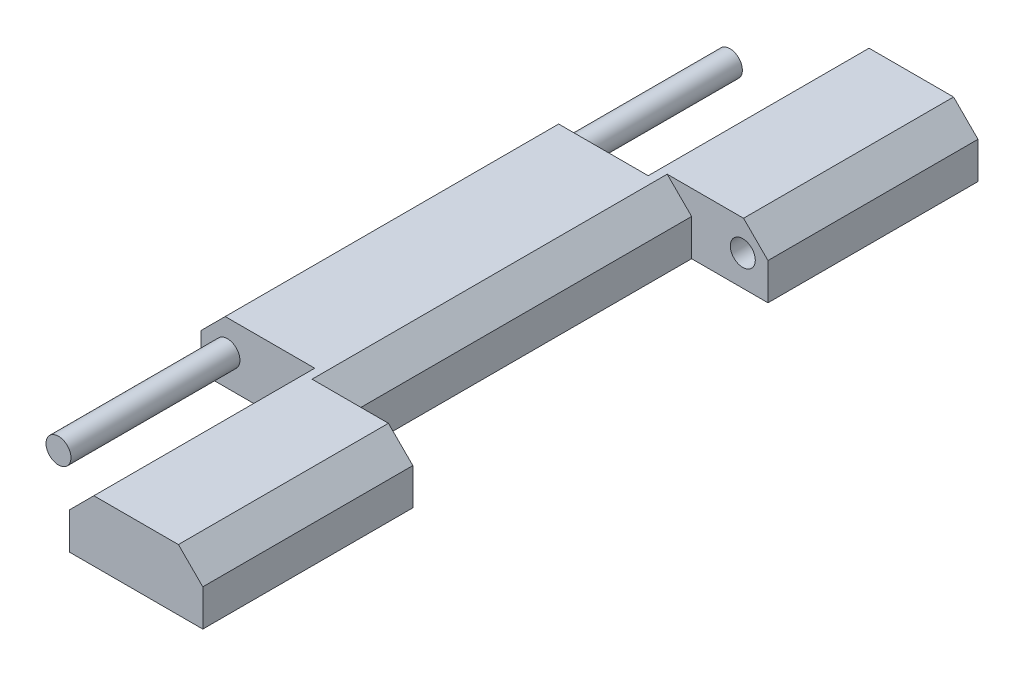
SolidWorks part; units mm, degrees
ref_plane "Front Plane" through (0, 0, 0) normal (0, 0, 1) x (1, 0, 0)
ref_plane "Top Plane" through (0, 0, 0) normal (0, 1, 0) x (1, 0, 0)
ref_plane "Right Plane" through (0, 0, 0) normal (1, 0, 0) x (0, 0, -1)
sketch "Sketch1" plane through (0, 0, 0) normal (0, 1, 0) x (1, 0, 0)
  line L0 (5.4621, -14.5454) -> (5.4621, -31.75)
  line L1 (-5.4621, 31.75) -> (5.4621, 31.75)
  line L2 (-5.4621, 31.75) -> (-5.4621, 13.6578)
  line L3 (-5.4621, -31.75) -> (5.4621, -31.75)
  line L4 (5.4621, 31.75) -> (5.4621, 14.5454)
  line L5 (-5.4621, -13.6578) -> (-5.4621, -31.75)
  line L7 (-12.7958, 13.6578) -> (-5.4621, 13.6578)
  line L8 (-12.7958, 13.6578) -> (-12.7958, -13.6578)
  line L9 (-12.7958, -13.6578) -> (-5.4621, -13.6578)
  line L13 (5.4621, -14.5454) -> (-0.7921, -14.5454)
  line L15 (5.4621, 14.5454) -> (-0.7921, 14.5454)
  line L16 (-0.7921, -14.5454) -> (-0.7921, 14.5454)
  point P0 (0, 0)
  point P6 (-7.9661, -1.326)
  point P12 (5.4621, 0)
  dimension "D1" = 63.5
extrude "Boss-Extrude1" add sketch "Sketch1" along normal blind 5
chamfer "Chamfer1" distance 2 angle 45 6 edges at (5.4621, 5, -23.1477) (-5.4621, 5, -22.7039) (-0.7921, 5, 0) (5.4621, 5, 23.1477) (-5.4621, 5, 22.7039) (-12.7958, 5, 0)
sketch "Sketch3" plane through (5.603, 0, 13.6578) normal (0, 0, 1) x (1, 0, 0)
  circle A0 centre (-16.2147, 2.5) radius 1.0217
ref_plane "Plane1" through (0, 0, 0) normal (0, 0, -1) x (-1, 0, 0)
extrude "Boss-Extrude2" add sketch "Sketch3" along normal mid plane 55 from surface contours A0 starting at plane "Plane1"
pattern_linear "LPattern5" [suppressed] count 14 spacing 20 of bodies 115 101
sketch "Sketch5" plane through (0, 0, -14.5454) normal (0, 0, 1) x (1, 0, 0)
  line L0 (-5.4621, 2.0622) -> (-0.7921, 2.0622)
  line L1 (-5.4621, 3) -> (-5.4621, 0) construction
  line L2 (-0.7921, 3) -> (-0.7921, 0) construction
  line L3 (-10.6117, 2.5) -> (-3.1271, 2.5)
  line L4 (-3.1271, 2.0622) -> (-3.1271, 2.5)
  line L5 (-3.1271, 2.5) -> (3.4003, 2.5)
  circle A0 centre (3.4003, 2.5) radius 1.0217
  circle A1 centre (-10.6117, 2.5) radius 1.0217 construction
extrude "Cut-Extrude1" cut sketch "Sketch5" against normal mid plane 55 from surface contours A0 starting at plane "Plane1"
scale "Scale1" scale about centroid uniform scaling yes scale factor 1.35
